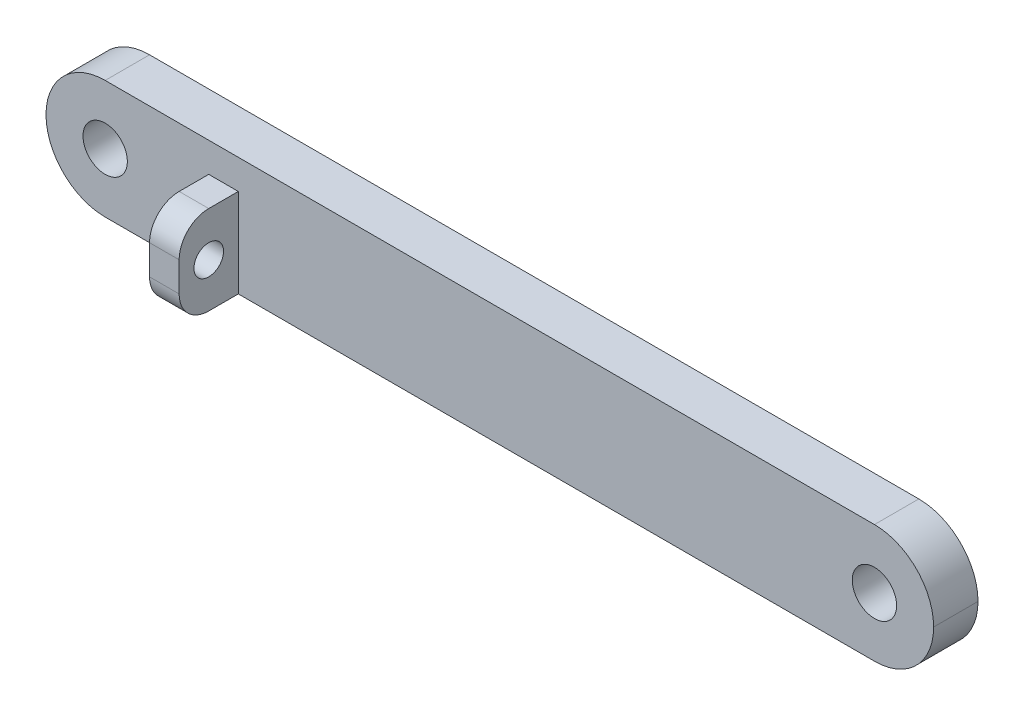
SolidWorks part; units mm, degrees
ref_plane "Płaszczyzna przednia" through (0, 0, 0) normal (0, 0, 1) x (1, 0, 0)
ref_plane "Płaszczyzna górna" through (0, 0, 0) normal (0, 1, 0) x (1, 0, 0)
ref_plane "Płaszczyzna prawa" through (0, 0, 0) normal (1, 0, 0) x (0, 0, -1)
sketch "Szkic1" plane through (0, 0, 0) normal (0, 0, 1) x (1, 0, 0)
  line L1 (0, 0) -> (60, 0)
  line L2 (0, 0) -> (0, 8)
  line L3 (0, 8) -> (60, 8)
  line L4 (60, 0) -> (60, 8)
extrude "Dodanie-wyciągnięcie1" add sketch "Szkic1" along normal blind 3
fillet "Zaokrąglenie1" radius 4 4 edges at (0, 0, 1.5) (0, 8, 1.5) (60, 8, 1.5) (60, 0, 1.5)
sketch "Szkic2" plane through (0, 0, 3) normal (0, 0, 1) x (1, 0, 0)
  circle A0 centre (4, 4) radius 1.5
  circle A1 centre (56, 4) radius 1.5
extrude "Wytnij-wyciągnięcie1" cut sketch "Szkic2" against normal blind 3
sketch "Szkic3" plane through (0, 0, 3) normal (0, 0, 1) x (1, 0, 0)
  line L0 (4, 0) -> (56, 0) construction
  line L5 (11, 0) -> (13, 0)
  line L6 (11, 0) -> (11, 6)
  line L7 (11, 6) -> (13, 6)
  line L8 (13, 0) -> (13, 6)
  point P4 (0, 0)
  point P7 (0, 0)
  point P8 (0, 0)
  point P9 (0, 0)
extrude "Dodanie-wyciągnięcie2" add sketch "Szkic3" along normal blind 4
sketch "Szkic4" plane through (11, 0, 0) normal (-1, 0, 0) x (0, 0, 1)
  circle A0 centre (5, 3) radius 1
extrude "Wytnij-wyciągnięcie2" cut sketch "Szkic4" against normal up to next
fillet "Zaokrąglenie2" radius 2 2 edges at (12, 6, 7) (12, 0, 7)
